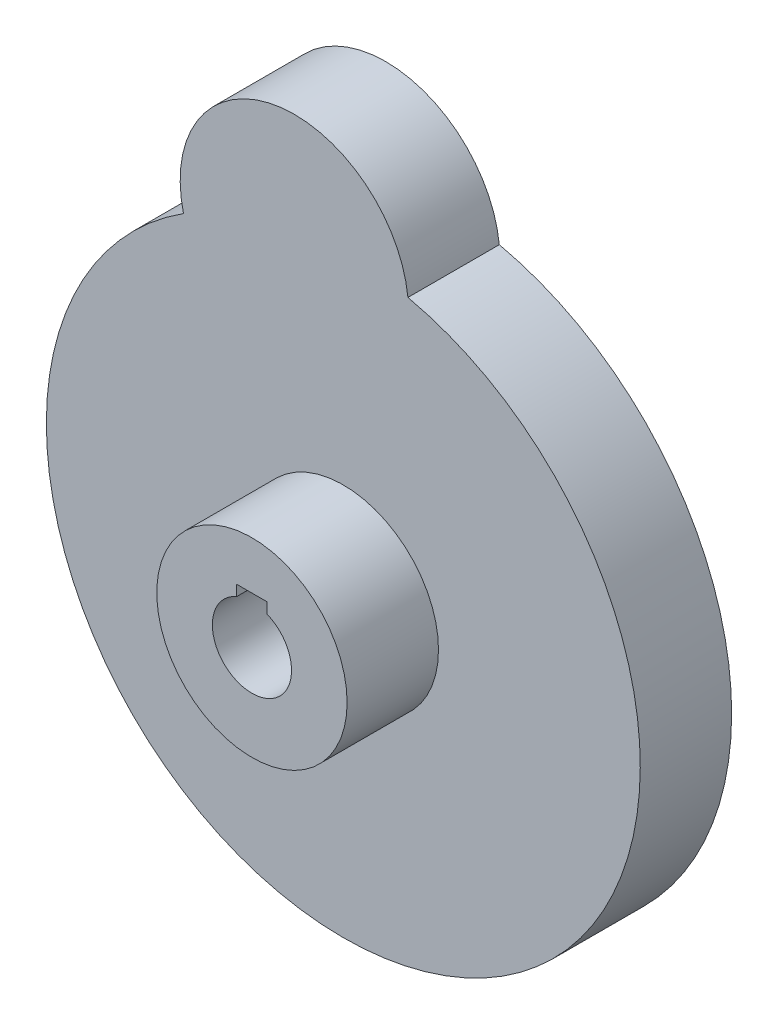
SolidWorks part; units mm, degrees
ref_plane "Front Plane" through (0, 0, 0) normal (0, 0, 1) x (1, 0, 0)
ref_plane "Top Plane" through (0, 0, 0) normal (0, 1, 0) x (1, 0, 0)
ref_plane "Right Plane" through (0, 0, 0) normal (1, 0, 0) x (0, 0, -1)
sketch "Sketch1" plane through (0, 0, 0) normal (0, 0, 1) x (1, 0, 0)
  line L0 (0, 0) -> (-6.425, 36.4379) construction
  line L1 (0, 0) -> (0, -46.5669) construction
  line L2 (0, 0) -> (0, 5.2) construction
  line L3 (0, 0) -> (0, 73.108) construction
  line L4 (-2, 6.2) -> (2, 6.2)
  line L5 (-2, 6.2) -> (-2, 4.2)
  line L6 (-2, 4.2) -> (2, 4.2)
  line L7 (2, 6.2) -> (2, 4.2)
  line L8 (-2, 6.2) -> (2, 4.2) construction
  line L9 (-2, 4.2) -> (2, 6.2) construction
  circle A0 centre (0, 0) radius 39
  circle A1 centre (0, 0) radius 12.5
  circle A2 centre (0, 0) radius 5.2
  circle A3 centre (-6.425, 36.4379) radius 15
  dimension "D1" = 78
  dimension "D3" = 30
  dimension "D5" = 10.4
  dimension "D6" = 25
  dimension "D2" = 10
  dimension "D4" = 37
  dimension "D7" = 2
  dimension "D8" = 4
extrude "Boss-Extrude1" add sketch "Sketch1" along normal blind 6 and the other way blind 6 contours A3 A0 A1 | A0 A3 | A0 A3 | A1 A2 L5 L4 L7 region at (-18.2114, -33.2419, 0) region at (-5.4197, 30.7365, 0) region at (-7.6202, 43.2162, 0) region at (-12.1464, 0, 0)
extrude "Boss-Extrude2" add sketch "Sketch1<4>" along normal blind 18 and the other way blind 18 contours A1 A2 L5 L4 L7 region at (-12.1464, 0, 0)
sketch "Sketch1<4>" plane through (0, 0, 0) normal (0, 0, 1) x (1, 0, 0) same geometry as "Sketch1"
